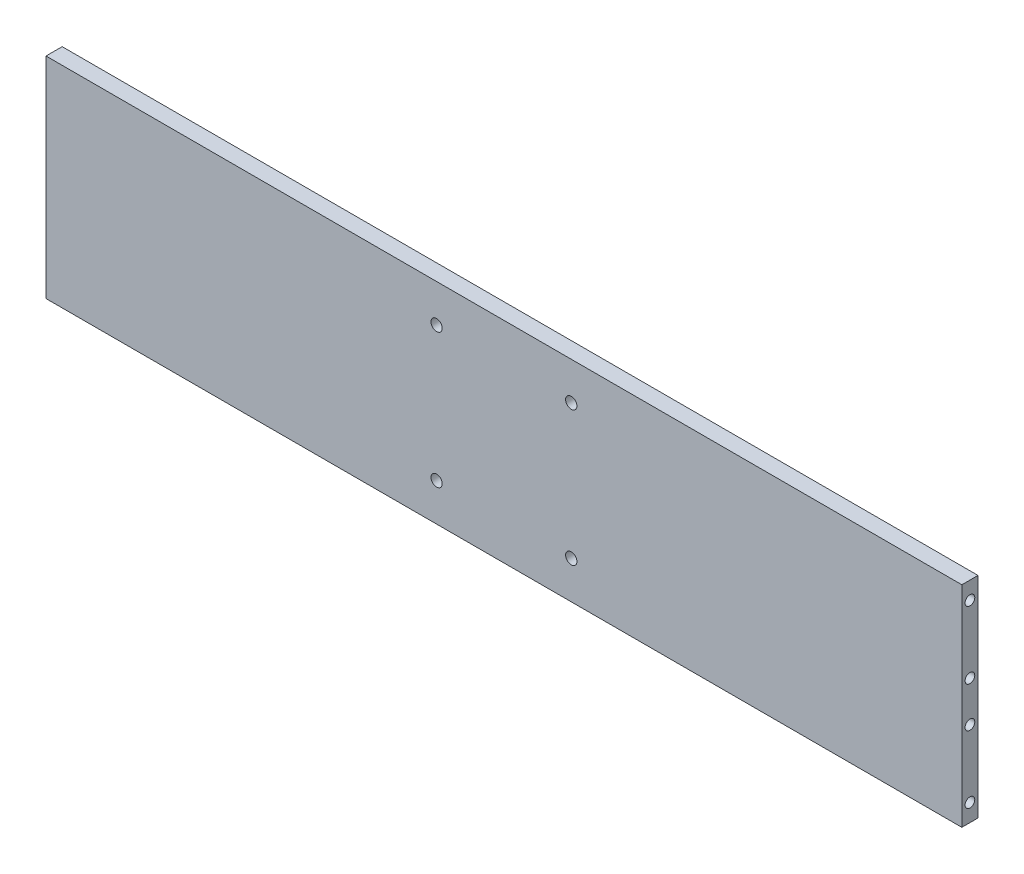
SolidWorks part; units mm, degrees
ref_plane "Front Plane" through (0, 0, 0) normal (0, 0, 1) x (1, 0, 0)
ref_plane "Top Plane" through (0, 0, 0) normal (0, 1, 0) x (1, 0, 0)
ref_plane "Right Plane" through (0, 0, 0) normal (1, 0, 0) x (0, 0, -1)
sketch "Sketch1" plane through (0, 0, 0) normal (0, 0, 1) x (1, 0, 0)
  line L1 (-170, -39) -> (170, -39)
  line L2 (-170, -39) -> (-170, 39)
  line L3 (-170, 39) -> (170, 39)
  line L4 (170, -39) -> (170, 39)
  line L5 (-170, -39) -> (170, 39) construction
  line L6 (-170, 39) -> (170, -39) construction
  line L7 (-25, -25) -> (25, -25) construction
  line L8 (-25, -25) -> (-25, 25) construction
  line L9 (-25, 25) -> (25, 25) construction
  line L10 (25, -25) -> (25, 25) construction
  line L11 (-25, -25) -> (25, 25) construction
  line L12 (-25, 25) -> (25, -25) construction
  circle A0 centre (-25, 25) radius 2.1
  circle A1 centre (25, 25) radius 2.1
  circle A2 centre (25, -25) radius 2.1
  circle A3 centre (-25, -25) radius 2.1
  point P0 (0, 0)
  point P6 (0, 0)
  dimension "D1" = 340
  dimension "D2" = 78
  dimension "D3" = 50
  dimension "D4" = 50
extrude "Boss-Extrude1" add sketch "Sketch1" along normal blind 6
sketch "Sketch2" plane through (170, 0, 0) normal (1, 0, 0) x (0, 0, -1)
  line L0 (-6, 0) -> (0, 0) construction
  line L1 (-6, -39) -> (-6, 39) construction
  line L2 (0, -39) -> (0, 39) construction
  line L3 (-3, 39) -> (-3, 0) construction
  line L4 (-6, 39) -> (0, 39) construction
  circle A0 centre (-3, 32.5) radius 1.8
  circle A1 centre (-3, 7.5) radius 1.8
  circle A2 centre (-3, -7.5) radius 1.8
  circle A3 centre (-3, -32.5) radius 1.8
  point P14 (-3, 19.5)
  dimension "D1" = 25
  dimension "D2" = 7.5
extrude "Cut-Extrude1" cut sketch "Sketch2" against normal up to next
